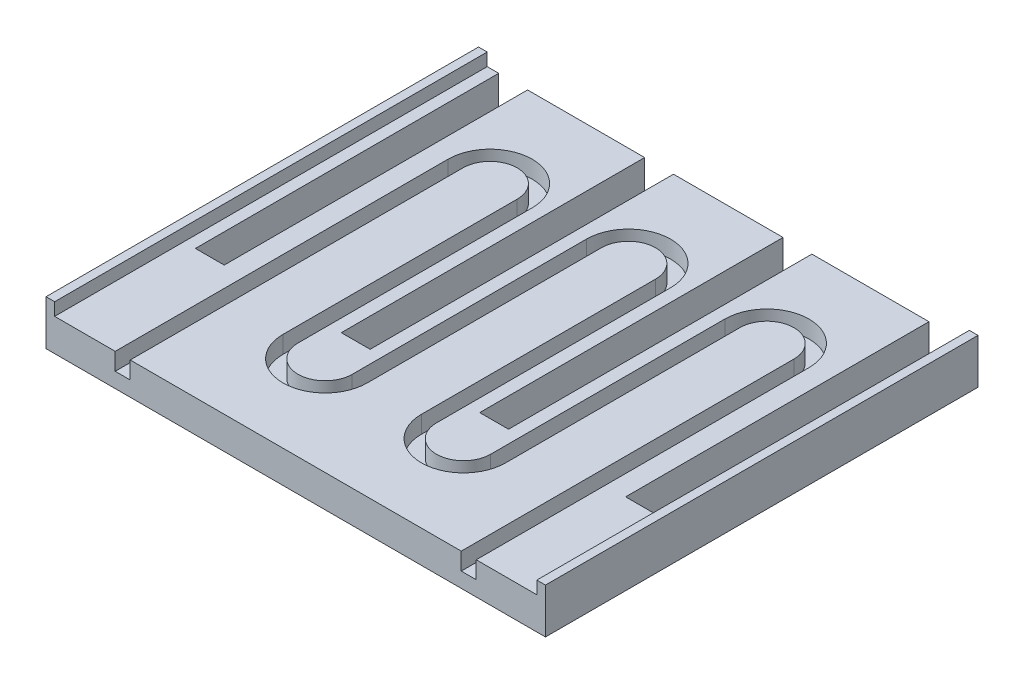
SolidWorks part; units mm, degrees
ref_plane "Спереди" through (0, 0, 0) normal (0, 0, 1) x (1, 0, 0)
ref_plane "Сверху" through (0, 0, 0) normal (0, 1, 0) x (1, 0, 0)
ref_plane "Справа" through (0, 0, 0) normal (1, 0, 0) x (0, 0, -1)
sketch "Подложка трубки" plane through (0, 0, 0) normal (0, 1, 0) x (1, 0, 0)
  line L0 (5.3073, 0.8937) -> (101.8191, 0.8937) construction
  line L1 (12, 0) -> (12, 50)
  line L2 (0, 0) -> (2.6, 0)
  line L3 (0, 0) -> (0, 50)
  line L4 (0, 50) -> (2.6, 50)
  line L5 (2.6, 0) -> (2.6, 50)
  line L6 (12, 0) -> (14.6, 0)
  line L7 (14.6, 0) -> (14.6, 50)
  line L8 (12, 50) -> (14.6, 50)
  line L9 (24, 0) -> (24, 50)
  line L10 (24, 0) -> (26.6, 0)
  line L11 (26.6, 0) -> (26.6, 50)
  line L12 (24, 50) -> (26.6, 50)
  line L13 (36, 0) -> (36, 50)
  line L14 (36, 0) -> (38.6, 0)
  line L15 (38.6, 0) -> (38.6, 50)
  line L16 (36, 50) -> (38.6, 50)
  line L17 (48, 0) -> (48, 50)
  line L18 (48, 0) -> (50.6, 0)
  line L19 (50.6, 0) -> (50.6, 50)
  line L20 (48, 50) -> (50.6, 50)
  line L21 (60, 0) -> (60, 50)
  line L22 (60, 0) -> (62.6, 0)
  line L23 (62.6, 0) -> (62.6, 50)
  line L24 (60, 50) -> (62.6, 50)
  line L25 (62.9198, 62.6) -> (-29.5124, 62.6) construction
  line L26 (0, 50) -> (14.6, 50)
  line L27 (0, 50) -> (0, 52.6)
  line L28 (0, 52.6) -> (14.6, 52.6)
  line L29 (14.6, 50) -> (14.6, 52.6)
  line L30 (24, 50) -> (38.6, 50)
  line L31 (24, 50) -> (24, 52.6)
  line L32 (24, 52.6) -> (38.6, 52.6)
  line L33 (38.6, 50) -> (38.6, 52.6)
  line L34 (48, 50) -> (62.6, 50)
  line L35 (48, 50) -> (48, 52.6)
  line L36 (48, 52.6) -> (62.6, 52.6)
  line L37 (62.6, 50) -> (62.6, 52.6)
  line L38 (12, 0) -> (26.6, 0)
  line L39 (12, 0) -> (12, -2.6)
  line L40 (12, -2.6) -> (26.6, -2.6)
  line L41 (26.6, 0) -> (26.6, -2.6)
  line L42 (36, 0) -> (50.6, 0)
  line L43 (36, 0) -> (36, -2.6)
  line L44 (36, -2.6) -> (50.6, -2.6)
  line L45 (50.6, 0) -> (50.6, -2.6)
  line L46 (0, 0) -> (2.6, 0)
  line L47 (0, 0) -> (0, -12.4)
  line L48 (0, -12.4) -> (2.6, -12.4)
  line L49 (2.6, 0) -> (2.6, -12.4)
  line L50 (60, 0) -> (62.6, 0)
  line L51 (60, 0) -> (60, -12.4)
  line L52 (60, -12.4) -> (62.6, -12.4)
  line L53 (62.6, 0) -> (62.6, -12.4)
  line L54 (-81.3744, -12.4) -> (67.7729, -12.4) construction
  line L55 (0, 62.7) -> (0, -70.5156) construction
  line L56 (26.25, -2.5) -> (26.25, -20) construction
  line L57 (-12, -12.4) -> (-12, 62.6)
  line L58 (74.6, -12.4) -> (74.6, 62.6) construction
  line L59 (62.6, 58.4344) -> (62.6, -75.5615) construction
  line L60 (-12, 62.6) -> (74.6, 62.6)
  line L61 (-12, 62.6) -> (-12, -12.4)
  line L62 (-12, -12.4) -> (74.6, -12.4)
  line L63 (74.6, 62.6) -> (74.6, -12.4)
  point P25 (0, -12.4)
  point P53 (74.6, 0.8937)
  point P55 (-12, 0.8937)
  point P60 (62.6, -12.4)
  point P64 (62.6, -12.4)
  dimension "D1" = 50
  dimension "D2" = 2.6
  dimension "D4" = 12
  dimension "D5" = 2.6
  dimension "D11" = 2.6
  dimension "D14" = 2.6
  dimension "D13" = 10
  dimension "D6" = 12
  dimension "D8" = 12
  dimension "D7" = 86.6
  dimension "D9" = 75
  dimension "D3" = 6
extrude "Бобышка-Вытянуть4" add sketch "Подложка трубки" along normal blind 5.6 contours L63 L60 L57 L62 L47 L3 L27 L28 L29 L7 L38 L9 L31 L32 L33 L15 L42 L17 L35 L36 L37 L23 L53 | L49 L62 L51 L21 L34 L19 L45 L44 L43 L13 L30 L11 L41 L40 L39 L1 L26 L5 region at (31.3, 0, -15.1213) region at (15.7456, 0, -25)
extrude "Бобышка-Вытянуть6" add sketch "Подложка трубки<9>" along normal blind 2.6 contours L49 L2 L47 L48 | L2 L5 L4 L3 | L41 L10 L38 L6 L39 L40 | L8 L1 L6 L7 | L12 L9 L10 L11 | L8 L29 L28 L27 L4 L26 | L16 L33 L32 L31 L12 L30 | L16 L13 L14 L15 | L45 L18 L42 L14 L43 L44 | L20 L17 L18 L19 | L24 L37 L36 L35 L20 L34 | L24 L21 L22 L23 | L51 L52 L53 L50 region at (13.3, 0, -25) region at (19.3, 0, 1.3) region at (7.3, 0, -51.3) region at (1.3, 0, -25) region at (25.3, 0, -25) region at (1.3, 0, 6.2) region at (31.3, 0, -51.3) region at (37.3, 0, -25) region at (61.3, 0, -25) region at (43.3, 0, 1.3) region at (55.3, 0, -51.3) region at (49.3, 0, -25)
sketch "Подложка трубки<9>" plane through (0, 0, 0) normal (0, 1, 0) x (1, 0, 0) same geometry as "Подложка трубки"
sketch "DS18B20" plane through (0, 5.6, 0) normal (0, 1, 0) x (1, 0, 0)
  line L0 (-12, 5) -> (74.6, 5)
  line L1 (-12, -12.4) -> (-12, 62.6) construction
  line L2 (74.6, 62.6) -> (74.6, -12.4) construction
  line L3 (14.6, 0) -> (24, 0) construction
  line L4 (-12, 16.3698) -> (0, 20.1)
  line L5 (0, 52.6) -> (0, -12.4) construction
  line L6 (14.6, 20.1) -> (24, 20.1)
  line L7 (14.6, 0) -> (14.6, 52.6) construction
  line L8 (24, 0) -> (24, 52.6) construction
  line L9 (38.6, 20.1) -> (48, 20.1)
  line L10 (38.6, 0) -> (38.6, 52.6) construction
  line L11 (48, 0) -> (48, 52.6) construction
  line L12 (62.6, 20.1) -> (74.6, 20.1)
  line L13 (62.6, -12.4) -> (62.6, 52.6) construction
  line L14 (62.6, -12.4) -> (62.6, 52.6) construction
  line L15 (-12, 62.6) -> (74.6, 62.6) construction
  line L16 (66.1, 62.6) -> (71.1, 62.6)
  line L17 (66.1, 62.6) -> (66.1, 10)
  line L18 (66.1, 10) -> (71.1, 10)
  line L19 (71.1, 62.6) -> (71.1, 10)
  line L20 (14.6, 0) -> (24, 0) construction
  line L21 (-8.5, 62.6) -> (-3.5, 62.6)
  line L22 (-8.5, 62.6) -> (-8.5, 10)
  line L23 (-8.5, 10) -> (-3.5, 10)
  line L24 (-3.5, 62.6) -> (-3.5, 10)
  line L25 (16.8, 62.6) -> (21.8, 62.6)
  line L26 (16.8, 62.6) -> (16.8, 10)
  line L27 (16.8, 10) -> (21.8, 10)
  line L28 (21.8, 62.6) -> (21.8, 10)
  line L30 (40.8, 62.6) -> (45.8, 62.6)
  line L31 (40.8, 62.6) -> (40.8, 10)
  line L32 (40.8, 10) -> (45.8, 10)
  line L33 (45.8, 62.6) -> (45.8, 10)
  line M3 (74.6, 62.6) -> (-12, 62.6)
  dimension "D4" = 12
  dimension "D1" = 5
  dimension "D6" = 5
  dimension "D7" = 9.4
  dimension "D8" = 2.2
  dimension "D2" = 2.2
  dimension "D3" = 3.5
  dimension "D5" = 3.5
  dimension "D9" = 10
extrude "Вырез-Вытянуть1" cut sketch "DS18B20" against normal blind 5 contours L24 L22 L4 M3 | L24 L4 L22 L23 | L28 L26 L6 M3 | L28 L6 L26 L27 | L33 L31 L9 M3 | L33 L9 L31 L32 | L19 L17 L12 M3 | L19 L12 L17 L18 region at (-6.0146, 5.6, -40.4152) region at (68.6, 5.6, -41.35) region at (43.3, 5.6, -41.35) region at (19.3, 5.6, -41.35) region at (-5.9214, 5.6, -14.1297) region at (19.3, 5.6, -15.05) region at (43.3, 5.6, -15.05) region at (68.6, 5.6, -15.05)
sketch "Эскиз7" plane through (0, 5.6, 0) normal (0, 1, 0) x (1, 0, 0)
  line L0 (-12, -12.4) -> (0, -12.4) construction
  line L1 (-12, 62.6) -> (-10.5, 62.6)
  line L2 (-12, 62.6) -> (-12, -12.4)
  line L3 (-12, -12.4) -> (-10.5, -12.4)
  line L4 (-10.5, 62.6) -> (-10.5, -12.4)
  line L5 (62.6, -12.4) -> (74.6, -12.4) construction
  line L6 (74.6, 62.6) -> (73.1, 62.6)
  line L7 (74.6, 62.6) -> (74.6, -12.4)
  line L8 (74.6, -12.4) -> (73.1, -12.4)
  line L9 (73.1, 62.6) -> (73.1, -12.4)
  dimension "D1" = 1.5
extrude "Бобышка-Вытянуть8" add sketch "Эскиз7" along normal blind 2.2
fillet "Скругление1" 2 edges at (60, 4.1, -50) (50.6, 4.1, -50) type full round first side face at (60, 4.1, -18.8) second side face at (50.6, 4.1, -23.7) middle face at (55.3, 4.1, -50)
fillet "Скругление2" 2 edges at (62.6, 4.1, -52.6) (48, 4.1, -52.6) type full round first side face at (62.6, 4.1, -20.1) second side face at (48, 4.1, -26.3) middle face at (55.3, 4.1, -52.6)
fillet "Скругление3" 2 edges at (48, 4.1, 0) (38.6, 4.1, 0) type full round first side face at (48, 4.1, -22.65) second side face at (38.6, 4.1, -26.3) middle face at (43.3, 4.1, 0)
fillet "Скругление4" 2 edges at (50.6, 4.1, 2.6) (36, 4.1, 2.6) type full round first side face at (50.6, 4.1, -21.35) second side face at (36, 4.1, -23.7) middle face at (43.3, 4.1, 2.6)
fillet "Скругление5" 2 edges at (36, 4.1, -50) (26.6, 4.1, -50) type full round first side face at (36, 4.1, -27.35) second side face at (26.6, 4.1, -23.7) middle face at (31.3, 4.1, -50)
fillet "Скругление6" 2 edges at (38.6, 4.1, -52.6) (24, 4.1, -52.6) type full round first side face at (38.6, 4.1, -28.65) second side face at (24, 4.1, -26.3) middle face at (31.3, 4.1, -52.6)
fillet "Скругление7" 2 edges at (26.6, 4.1, 2.6) (12, 4.1, 2.6) type full round first side face at (26.6, 4.1, -21.35) second side face at (12, 4.1, -23.7) middle face at (19.3, 4.1, 2.6)
fillet "Скругление8" 2 edges at (14.6, 4.1, 0) (24, 4.1, 0) type full round first side face at (14.6, 4.1, -26.3) second side face at (24, 4.1, -22.65) middle face at (19.3, 4.1, 0)
fillet "Скругление9" 2 edges at (12, 4.1, -50) (2.6, 4.1, -50) type full round first side face at (12, 4.1, -27.35) second side face at (2.6, 4.1, -18.8) middle face at (7.3, 4.1, -50)
fillet "Скругление10" 2 edges at (14.6, 4.1, -52.6) (0, 4.1, -52.6) type full round first side face at (14.6, 4.1, -28.65) second side face at (0, 4.1, -20.1) middle face at (7.3, 4.1, -52.6)
equation "\"Tube\" = 2.6"
equation "\"D5@Подложка трубки\"=\"Tube\""
equation "\"D11@Подложка трубки\"=\"Tube\""
equation "\"D14@Подложка трубки\"=\"Tube\""
equation "\"D2@Подложка трубки\"=\"Tube\""
equation "\"Offset1\" = 12"
equation "\"D6@Подложка трубки\"=\"Offset1\""
equation "\"D8@Подложка трубки\"=\"Offset1\""
equation "\"Height\"= 3 + \"Tube\""
equation "\"D1@Бобышка-Вытянуть4\"=\"Height\""
equation "\"D1@Бобышка-Вытянуть6\"=\"Tube\""
equation "\"Pattern\" = 12"
equation "\"D4@Подложка трубки\"=\"Pattern\""
equation "\"Temp\" = 5"
equation "\"tempOffset\" = 5"
equation "\"D1@DS18B20\" = \"tempOffset\""
equation "\"D6@DS18B20\" = \"Temp\""
equation "\"D8@DS18B20\" =  ( \"D7@DS18B20\" - \"Temp\" )  / 2"
equation "\"D2@DS18B20\" =  ( \"D7@DS18B20\" - \"Temp\" )  / 2"
equation "\"D3@DS18B20\" =  ( \"D4@DS18B20\" - \"Temp\" )  / 2"
equation "\"D5@DS18B20\" =  ( \"D4@DS18B20\" - \"Temp\" )  / 2"
equation "\"D1@Вырез-Вытянуть1\"=\"Temp\""
